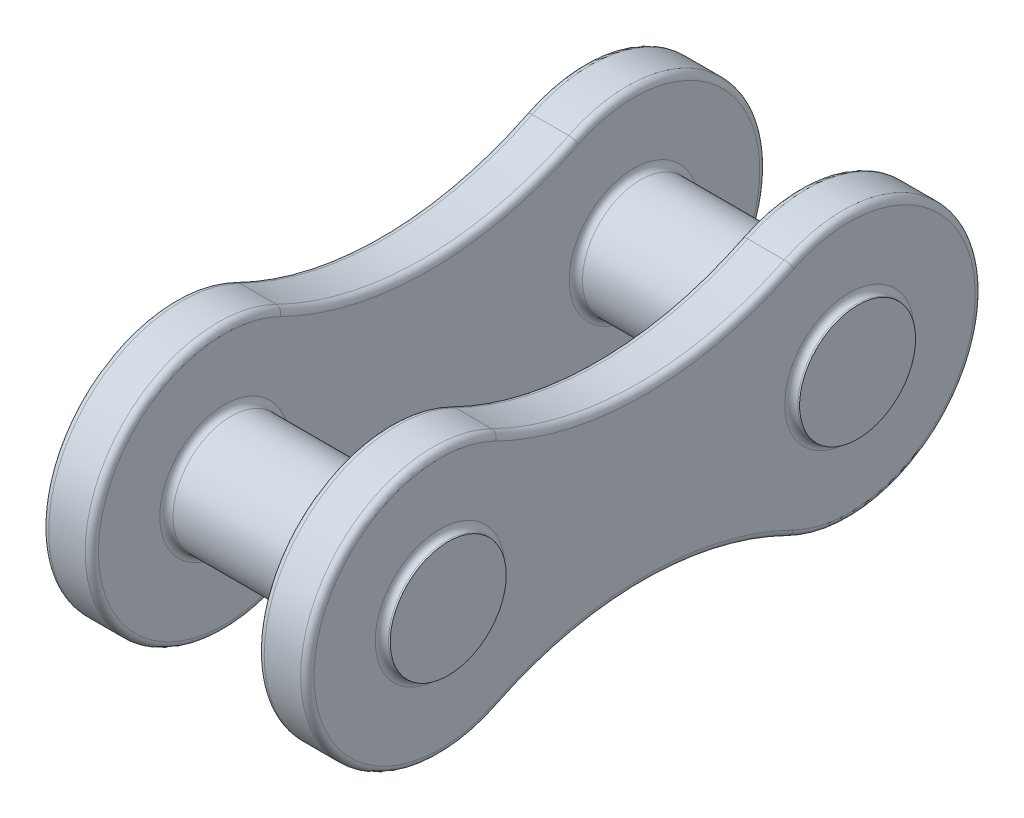
SolidWorks part; units mm, degrees
ref_plane "Alzado" through (0, 0, 0) normal (0, 0, 1) x (1, 0, 0)
ref_plane "Planta" through (0, 0, 0) normal (0, 1, 0) x (1, 0, 0)
ref_plane "Vista lateral" through (0, 0, 0) normal (1, 0, 0) x (0, 0, -1)
sketch "Croquis1" plane through (0, 0, 0) normal (1, 0, 0) x (0, 0, -1)
  line L0 (0, 4.7813) -> (0, -4.7813) construction
  line L1 (-6.175, 0) -> (6.175, 0) construction
  circle A0 centre (-6.175, 0) radius 1.75
  arc A1 (-4.4107, 3.5899) -> (-4.4107, -3.5899) centre (-6.175, 0) ccw
  circle A2 centre (6.175, 0) radius 1.75
  arc A3 (4.4107, 3.5899) -> (4.4107, -3.5899) centre (6.175, 0) cw
  arc A4 (-4.4107, 3.5899) -> (4.4107, 3.5899) centre (0, 12.5646) ccw
  arc A5 (-4.4107, -3.5899) -> (4.4107, -3.5899) centre (0, -12.5646) cw
  point P4 (0, 0)
  point P8 (0, 0)
  dimension "D2" = 3.5
  dimension "D3" = 8
  dimension "D4" = 10
  dimension "D1" = 12.35
extrude "Saliente-Extruir1" add sketch "Croquis1" along normal blind 1.5 from offset 2.5
sketch "Croquis2" plane through (0, 0, 0) normal (1, 0, 0) x (0, 0, -1)
  circle A0 centre (6.175, 0) radius 1.75 construction
  circle A1 centre (-6.175, 0) radius 1.75 construction
  circle A2 centre (6.175, 0) radius 1.75
  circle A3 centre (-6.175, 0) radius 1.75
  arc A4 (-4.4107, 3.5899) -> (4.4107, 3.5899) centre (0, 12.5646) ccw
  arc A5 (-4.4107, 3.5899) -> (-4.4107, -3.5899) centre (-6.175, 0) ccw
  arc A6 (4.4107, -3.5899) -> (-4.4107, -3.5899) centre (0, -12.5646) ccw
  arc A7 (4.4107, -3.5899) -> (4.4107, 3.5899) centre (6.175, 0) ccw
  arc A8 (-4.4107, 3.5899) -> (4.4107, 3.5899) centre (0, 12.5646) ccw
  arc A9 (-4.4107, 3.5899) -> (-4.4107, -3.5899) centre (-6.175, 0) ccw
  arc A10 (4.4107, -3.5899) -> (-4.4107, -3.5899) centre (0, -12.5646) ccw
  arc A11 (4.4107, -3.5899) -> (4.4107, 3.5899) centre (6.175, 0) ccw
  dimension "D1" = 0
extrude "Saliente-Extruir2" add sketch "Croquis2" against normal blind 1.5 from offset 2.5 separate body offset against normal yes
sketch "Croquis3" plane through (0, 0, 0) normal (1, 0, 0) x (0, 0, -1)
  circle A0 centre (6.175, 0) radius 1.75 construction
  circle A1 centre (-6.175, 0) radius 1.75 construction
  circle A2 centre (6.175, 0) radius 1.75
  circle A3 centre (-6.175, 0) radius 1.75
extrude "Saliente-Extruir3" add sketch "Croquis3" along normal mid plane 8.5
fillet "Redondeo1" radius 0.2 24 edges at (2.5, 0, -7.925) (2.5, 0, 4.425) (2.5, 0, 10.175) (2.5, -2.5646, 0) (2.5, 0, -10.175) (2.5, 2.5646, 0) (-4, -2.5646, 0) (-4, 0, -10.175) (-4, 2.5646, 0) (-4, 0, 10.175) (-4, 0, -7.925) (-4, 0, 4.425) (-2.5, 2.5646, 0) (-2.5, 0, -10.175) (-2.5, -2.5646, 0) (-2.5, 0, 10.175) (-2.5, 0, -7.925) (-2.5, 0, 4.425) (4, 0, -4.425) (4, 0, -10.175) (4, -2.5646, 0) (4, 0, 10.175) (4, 2.5646, 0) (4, 0, 4.425)
